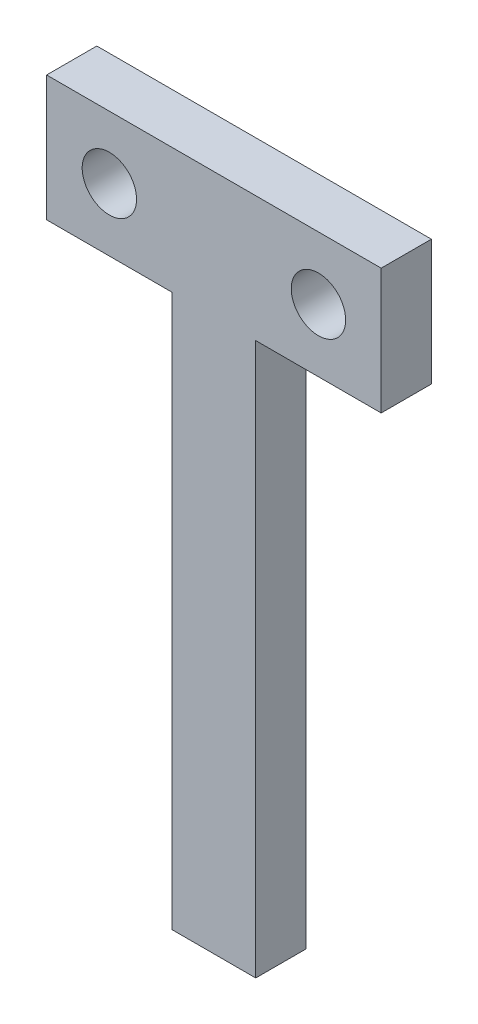
SolidWorks part; units mm, degrees
ref_plane "Front Plane" through (0, 0, 0) normal (0, 0, 1) x (1, 0, 0)
ref_plane "Top Plane" through (0, 0, 0) normal (0, 1, 0) x (1, 0, 0)
ref_plane "Right Plane" through (0, 0, 0) normal (1, 0, 0) x (0, 0, -1)
sketch "Sketch1" plane through (0, 0, 0) normal (0, 0, 1) x (1, 0, 0)
  line L0 (0, 0) -> (0, 33)
  line L1 (0, 33) -> (-7.5, 33)
  line L2 (-7.5, 33) -> (-7.5, 40.5)
  line L3 (-7.5, 40.5) -> (12.5, 40.5)
  line L4 (12.5, 40.5) -> (12.5, 33)
  line L5 (12.5, 33) -> (5, 33)
  line L6 (5, 33) -> (5, 0)
  line L7 (5, 0) -> (0, 0)
  circle A0 centre (-3.75, 36.75) radius 1.625
  circle A1 centre (8.75, 36.75) radius 1.625
  point P13 (12.5, 36.75)
  point P15 (-3.75, 33)
  point P17 (8.75, 33)
  dimension "D6" = 3.25
  dimension "D1" = 5
  dimension "D2" = 7.5
  dimension "D4" = 7.5
  dimension "D5" = 33
extrude "Boss-Extrude1" add sketch "Sketch1" along normal blind 3
